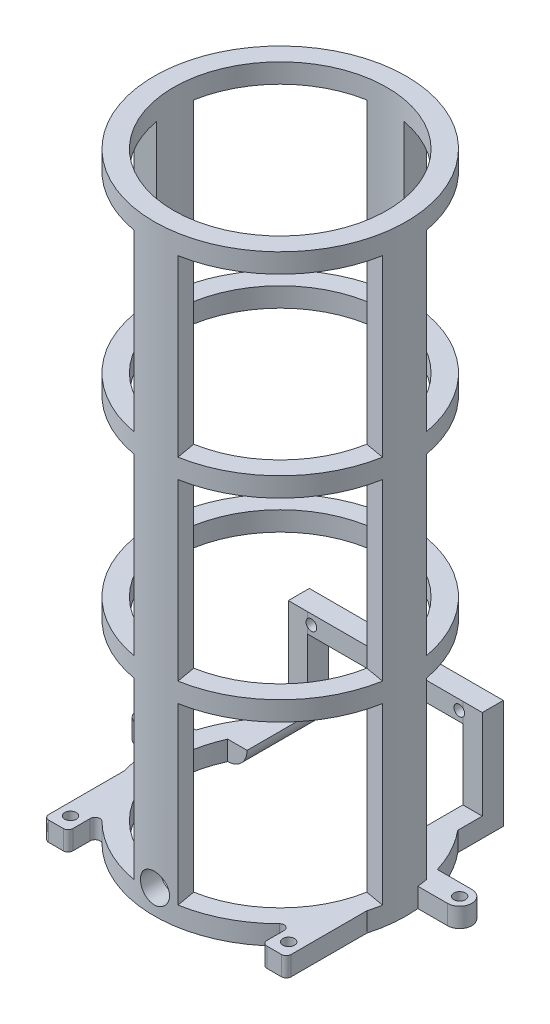
SolidWorks part; units mm, degrees
ref_plane "Front Plane" through (0, 0, 0) normal (0, 0, 1) x (1, 0, 0)
ref_plane "Top Plane" through (0, 0, 0) normal (0, 1, 0) x (1, 0, 0)
ref_plane "Right Plane" through (0, 0, 0) normal (1, 0, 0) x (0, 0, -1)
sketch "Sketch1" plane through (0, 0, 0) normal (0, 1, 0) x (1, 0, 0)
  circle A0 centre (0, 0) radius 22
  circle A1 centre (0, 0) radius 26
  dimension "D1" = 44
  dimension "D2" = 4
extrude "Boss-Extrude1" add sketch "Sketch1" along normal blind 4
sketch "Sketch2" plane through (0, 0, 0) normal (0, 1, 0) x (1, 0, 0)
  line L0 (0, 0) -> (0, 26.5919) construction
  line L1 (-4.5149, 25.605) -> (-3.8203, 21.6658)
  line L2 (-4.5149, 25.605) -> (0, 0) construction
  line L3 (4.5149, 25.605) -> (3.8203, 21.6658)
  line L4 (25.605, 4.5149) -> (21.6658, 3.8203)
  line L5 (25.605, -4.5149) -> (21.6658, -3.8203)
  line L6 (4.5149, -25.605) -> (3.8203, -21.6658)
  line L7 (-4.5149, -25.605) -> (-3.8203, -21.6658)
  line L8 (-25.605, -4.5149) -> (-21.6658, -3.8203)
  line L9 (-25.605, 4.5149) -> (-21.6658, 3.8203)
  circle A0 centre (0, 0) radius 26 construction
  circle A1 centre (0, 0) radius 22 construction
  arc A2 (4.5149, 25.605) -> (-4.5149, 25.605) centre (0, 0) ccw
  arc A3 (3.8203, 21.6658) -> (-3.8203, 21.6658) centre (0, 0) ccw
  arc A4 (25.605, -4.5149) -> (25.605, 4.5149) centre (0, 0) ccw
  arc A5 (21.6658, -3.8203) -> (21.6658, 3.8203) centre (0, 0) ccw
  arc A6 (-4.5149, -25.605) -> (4.5149, -25.605) centre (0, 0) ccw
  arc A7 (-3.8203, -21.6658) -> (3.8203, -21.6658) centre (0, 0) ccw
  arc A8 (-25.605, 4.5149) -> (-25.605, -4.5149) centre (0, 0) ccw
  arc A9 (-21.6658, 3.8203) -> (-21.6658, -3.8203) centre (0, 0) ccw
  point P23 (0, 0)
  dimension "D1" = 10
  dimension "D2" = 4
extrude "Boss-Extrude2" add sketch "Sketch2" along normal blind 120 from surface starting at face at (0, 4, 26)
extrude "Boss-Extrude3" add sketch "Sketch1<2>" along normal blind 4 from offset 40
sketch "Sketch1<2>" plane through (0, 0, 0) normal (0, 1, 0) x (1, 0, 0) same geometry as "Sketch1"
extrude "Boss-Extrude4" add sketch "Sketch1<3>" along normal blind 4 from offset 80
sketch "Sketch1<3>" plane through (0, 0, 0) normal (0, 1, 0) x (1, 0, 0) same geometry as "Sketch1"
extrude "Boss-Extrude5" add sketch "Sketch1<4>" along normal blind 4 from offset 120
sketch "Sketch1<4>" plane through (0, 0, 0) normal (0, 1, 0) x (1, 0, 0) same geometry as "Sketch1"
sketch "Sketch3" plane through (0, 0, 0) normal (0, 1, 0) x (1, 0, 0)
  line L0 (0, 0) -> (0, 39.1245) construction
  line L1 (0, 0) -> (-34.0474, 0) construction
  line L2 (-24.8948, 7.5) -> (-32, 7.5)
  line L3 (-25.8795, 2.5) -> (-32, 2.5)
  line L4 (25.8795, 2.5) -> (32, 2.5)
  line L5 (24.8948, 7.5) -> (32, 7.5)
  circle A0 centre (0, 0) radius 26 construction
  arc A1 (-32, 7.5) -> (-32, 2.5) centre (-32, 5) ccw
  arc A2 (-24.8948, 7.5) -> (-25.8795, 2.5) centre (0, 0) ccw
  circle A3 centre (-32, 5) radius 1.2
  circle A4 centre (32, 5) radius 1.2
  arc A5 (24.8948, 7.5) -> (25.8795, 2.5) centre (0, 0) cw
  arc A6 (32, 7.5) -> (32, 2.5) centre (32, 5) cw
  dimension "D2" = 32
  dimension "D4" = 2.4
  dimension "D1" = 5
  dimension "D3" = 5
extrude "Boss-Extrude6" add sketch "Sketch3" along normal blind 4
sketch "Sketch4" plane through (0, 0, 0) normal (0, 0, 1) x (1, 0, 0)
  line L1 (-20, -22.5) -> (20, -22.5)
  line L2 (-20, -22.5) -> (-20, 22.5)
  line L3 (-20, 22.5) -> (20, 22.5)
  line L4 (20, -22.5) -> (20, 22.5)
  line L5 (-20, -22.5) -> (20, 22.5) construction
  line L6 (-20, 22.5) -> (20, -22.5) construction
  point P0 (0, 0)
  dimension "D1" = 40
  dimension "D2" = 45
extrude "Cut-Extrude1" cut sketch "Sketch4" against normal through all
sketch "Sketch6" plane through (0, 0, 0) normal (0, 1, 0) x (1, 0, 0)
  line L0 (20, 9.1652) -> (20, 16.6132) construction
  line L1 (-20, 16.6132) -> (-20, 9.1652) construction
  line L2 (20, 9.1652) -> (20, 16.6132)
  line L3 (-20, 16.6132) -> (-20, 9.1652)
  line L4 (-20, 26) -> (20, 26)
  line L5 (20, 16.6132) -> (20, 26)
  line L6 (-20, 16.6132) -> (-20, 26)
  line L7 (-20, 9.1652) -> (-16, 9.1652)
  line L8 (-16, 21.67) -> (16, 21.67)
  line L9 (-16, 21.67) -> (-16, 9.1652)
  line L10 (20, 9.1652) -> (16, 9.1652)
  line L11 (16, 9.1652) -> (16, 21.67)
  circle A0 centre (0, 0) radius 26 construction
  circle A3 centre (0, 0) radius 22 construction
  point P4 (0, 26)
  point P10 (0, 26)
  point P11 (0, 22)
  point P17 (0, 21.67)
  dimension "D1" = 4
  dimension "D2" = 4
  dimension "D3" = 4.33
extrude "Boss-Extrude7" add sketch "Sketch6" along normal up to surface (22.5 mm away) up to face at (0, 22.5, -23.8177)
sketch "Sketch7" plane through (0, 0, 0) normal (0, 0, 1) x (1, 0, 0)
  line L0 (20, 0) -> (-20, 0) construction
  line L1 (16, 0) -> (-16, 0)
  line L2 (16, 0) -> (16, 18.5)
  line L3 (16, 18.5) -> (-16, 18.5)
  line L4 (-16, 0) -> (-16, 18.5)
  line L5 (20, 22.5) -> (20, 0) construction
  line L6 (-20, 22.5) -> (-20, 0) construction
  line L7 (20, 22.5) -> (0, 22.5) construction
  dimension "D1" = 4
  dimension "D2" = 4
  dimension "D3" = 4
extrude "Cut-Extrude2" cut sketch "Sketch7" against normal through all
fillet "Fillet1" radius 4 2 edges at (16, 0, -17.5826) (-16, 0, -17.5826)
sketch "Sketch8" plane through (0, 0, 0) normal (1, 0, 0) x (0, 0, -1)
  line L1 (9.1652, 22.5) -> (21.6658, 22.5)
  line L2 (9.1652, 22.5) -> (9.1652, 4)
  line L3 (9.1652, 4) -> (21.6658, 4)
  line L4 (21.6658, 22.5) -> (21.6658, 4)
  line L5 (9.1652, 22.5) -> (26, 22.5) construction
  line L6 (4.5149, 4) -> (2.5, 4) construction
  line L7 (21.6658, 40) -> (21.6658, 22.5) construction
  line L8 (21.6658, 40) -> (21.6658, 22.5) construction
extrude "Cut-Extrude3" cut sketch "Sketch8" against normal through all both and the other way through all
sketch "Sketch9" plane through (0, 0, 0) normal (0, 1, 0) x (1, 0, 0)
  line L0 (0, 0) -> (0, -43.6925) construction
  line L1 (-25, -7.1414) -> (-25, -23.75)
  line L3 (-20, -16.6132) -> (-20, -23.75)
  line L5 (-25, -23.75) -> (-20, -23.75)
  line L6 (25, -23.75) -> (20, -23.75)
  line L7 (20, -16.6132) -> (20, -23.75)
  line L8 (25, -7.1414) -> (25, -23.75)
  circle A0 centre (-22.5, -20.75) radius 1.2 construction
  circle A1 centre (-22.5, -20.75) radius 1.2
  circle A2 centre (0, 0) radius 26 construction
  arc A3 (-25, -7.1414) -> (-20, -16.6132) centre (0, 0) ccw
  arc A4 (25, -7.1414) -> (20, -16.6132) centre (0, 0) cw
  circle A5 centre (22.5, -20.75) radius 1.2
  dimension "D3" = 3
  dimension "D1" = 2.5
  dimension "D2" = 2.5
extrude "Boss-Extrude8" add sketch "Sketch9" along normal up to surface (4 mm away) from surface up to face at (-15.436, 4, 15.436) starting at face at (0, 0, -2.6986)
fillet "Fillet2" radius 1 6 edges at (-25, 2, 23.75) (-20, 2, 23.75) (-20, 2, 16.6132) (20, 2, 16.6132) (25, 2, 23.75) (20, 2, 23.75)
sketch "Sketch10" plane through (0, 0, 0) normal (0, 0, 1) x (1, 0, 0)
  circle A0 centre (0, 5) radius 3
  dimension "D1" = 6
  dimension "D2" = 5
extrude "Cut-Extrude4" cut sketch "Sketch10" along normal through all
sketch "Sketch11" plane through (0, 0, 0) normal (0, 0, 1) x (1, 0, 0)
  line L0 (0, 22.5) -> (0, 18.5) construction
  line L1 (16, 18.5) -> (-16, 18.5) construction
  line L2 (20, 20.5) -> (-20, 20.5) construction
  line L3 (-20, 22.5) -> (-20, 0) construction
  line L5 (17.5, 9.875) -> (-17.5, 9.875) construction
  line L6 (17.5, 9.875) -> (17.5, 31.125) construction
  line L7 (17.5, 31.125) -> (-17.5, 31.125) construction
  line L8 (-17.5, 9.875) -> (-17.5, 31.125) construction
  line L9 (17.5, 9.875) -> (-17.5, 31.125) construction
  line L10 (17.5, 31.125) -> (-17.5, 9.875) construction
  circle A0 centre (-15.25, 20.5) radius 1.1
  circle A1 centre (15.25, 20.5) radius 1.1
  point P10 (0, 20.5)
  point P14 (0, 20.5)
  dimension "D1" = 2.2
  dimension "D2" = 30.5
  dimension "D3" = 21.25
  dimension "D4" = 35
extrude "Cut-Extrude5" cut sketch "Sketch11" along normal up to surface (4.3342 mm away) from surface up to face at (-18, 13.25, -21.6658) starting at face at (0, 12.3159, -26)
